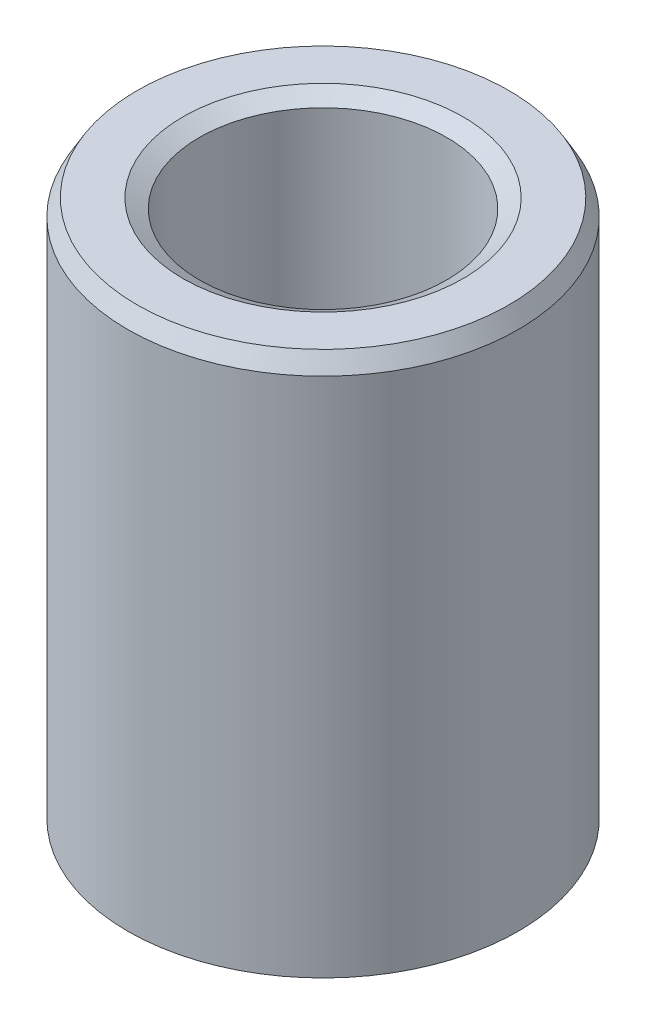
SolidWorks part; units mm, degrees
ref_plane "Front Plane" through (0, 0, 0) normal (0, 0, 1) x (1, 0, 0)
ref_plane "Top Plane" through (0, 0, 0) normal (0, 1, 0) x (1, 0, 0)
ref_plane "Right Plane" through (0, 0, 0) normal (1, 0, 0) x (0, 0, -1)
sketch "Sketch1" plane through (0, 0, 0) normal (0, 1, 0) x (1, 0, 0)
  circle A0 centre (0, 0) radius 25
  dimension "SLEEVE_OD" = 50
extrude "Boss-Extrude1" add sketch "Sketch1" along normal blind 70.0366
sketch "Sketch2" plane through (0, 0, 0) normal (0, 1, 0) x (1, 0, 0)
  circle A0 centre (0, 0) radius 15.8219
  dimension "BORE_D" = 31.6438
extrude "Cut-Extrude1" cut sketch "Sketch2" along normal through all
chamfer "Chamfer1" distance 2.112 angle 30 4 edges at (0, 70.0366, 15.8219) (0, 0, 15.8219) (0, 0, 25) (0, 70.0366, 25) first distance on face at (0, 70.0366, 15.8219) first distance on face at (0, 0, 15.8219) first distance on face at (0, 70.0366, 25)
